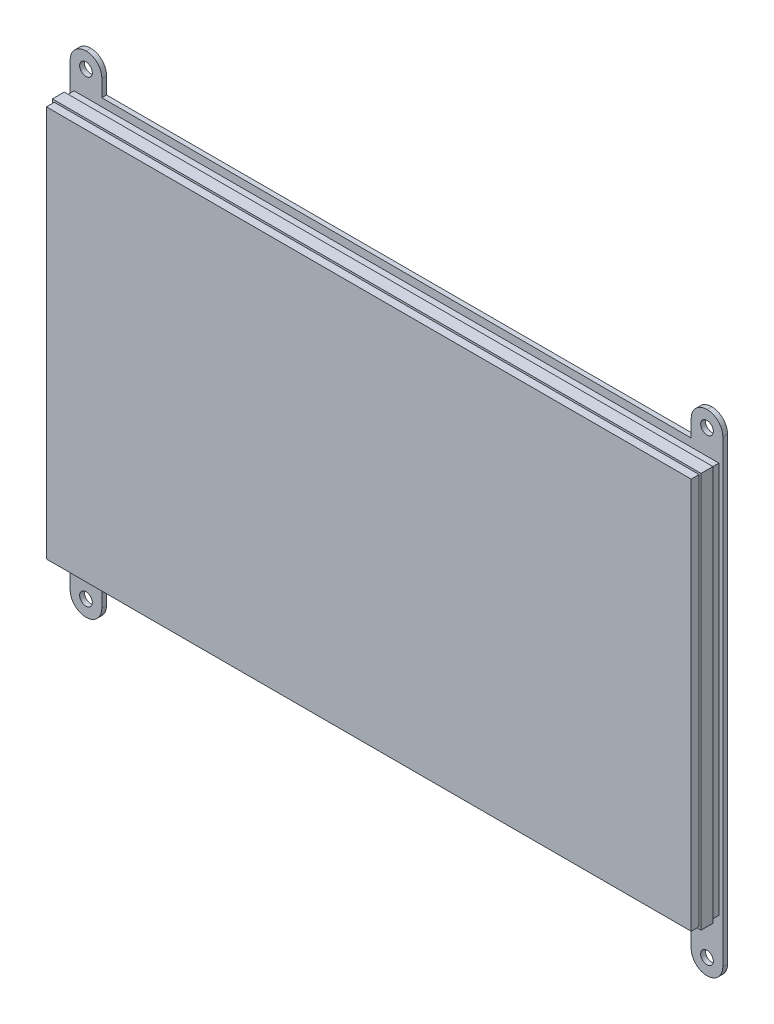
SolidWorks part; units mm, degrees
material "Alliage 2018"
ref_plane "Plan de face" through (0, 0, 0) normal (0, 0, 1) x (1, 0, 0)
ref_plane "Plan de dessus" through (0, 0, 0) normal (0, 1, 0) x (1, 0, 0)
ref_plane "Plan de droite" through (0, 0, 0) normal (1, 0, 0) x (0, 0, -1)
sketch "Esquisse1" plane through (0, 0, 0) normal (0, 0, 1) x (1, 0, 0)
  line L0 (0, 58.5) -> (0, -58.5) construction
  line L1 (-74.5, 53.75) -> (74.5, 53.75)
  line L2 (-82.5, 53.5) -> (-82.5, -53.5)
  line L3 (-74.5, -53.75) -> (74.5, -53.75)
  line L4 (82.5, 53.5) -> (82.5, -53.5)
  line L5 (-82.5, 53.5) -> (82.5, -53.5) construction
  line L6 (-82.5, -53.5) -> (82.5, 53.5) construction
  line L7 (-82, 52.25) -> (82, 52.25)
  line L8 (-82, 52.25) -> (-82, -47.75)
  line L9 (-82, -47.75) -> (82, -47.75)
  line L10 (82, 52.25) -> (82, -47.75)
  line L12 (-82.5, 53.5) -> (-82.5, 58.01)
  line L13 (-78.51, 62) -> (-78.49, 62)
  line L14 (-74.5, 53.75) -> (-74.5, 58.01)
  line L15 (82.5, 0) -> (-82.5, 0) construction
  line L16 (74.5, 53.75) -> (74.5, 58.01)
  line L17 (78.51, 62) -> (78.49, 62)
  line L18 (82.5, 53.5) -> (82.5, 58.01)
  line L19 (-81.5, -47.25) -> (81.5, -47.25)
  line L20 (-81.5, -47.25) -> (-81.5, 51.75)
  line L21 (82.5, -53.5) -> (82.5, -58.01)
  line L22 (78.51, -62) -> (78.49, -62)
  line L23 (74.5, -53.75) -> (74.5, -58.01)
  line L24 (-74.5, -53.75) -> (-74.5, -58.01)
  line L25 (-78.51, -62) -> (-78.49, -62)
  line L26 (-82.5, -53.5) -> (-82.5, -58.01)
  line L27 (-81.5, 51.75) -> (81.5, 51.75)
  line L28 (81.5, -47.25) -> (81.5, 51.75)
  circle A0 centre (-78.5, 58) radius 1.6
  arc A1 (-78.49, 62) -> (-74.5, 58.01) centre (-78.49, 58.01) cw
  arc A2 (-82.5, 58.01) -> (-78.51, 62) centre (-78.51, 58.01) cw
  arc A3 (82.5, 58.01) -> (78.51, 62) centre (78.51, 58.01) ccw
  arc A4 (78.49, 62) -> (74.5, 58.01) centre (78.49, 58.01) ccw
  circle A5 centre (78.5, 58) radius 1.6
  circle A6 centre (78.5, -58) radius 1.6
  arc A7 (78.49, -62) -> (74.5, -58.01) centre (78.49, -58.01) cw
  arc A8 (82.5, -58.01) -> (78.51, -62) centre (78.51, -58.01) cw
  arc A9 (-82.5, -58.01) -> (-78.51, -62) centre (-78.51, -58.01) ccw
  arc A10 (-78.49, -62) -> (-74.5, -58.01) centre (-78.49, -58.01) ccw
  circle A11 centre (-78.5, -58) radius 1.6
  point P0 (0, 0)
  point P21 (-74.5, 62)
  point P24 (-82.5, 62)
  point P34 (82.5, 62)
  point P35 (74.5, 62)
  point P45 (74.5, -62)
  point P46 (82.5, -62)
  point P56 (-82.5, -62)
  point P57 (-74.5, -62)
  dimension "D5" = 4.25
  dimension "D6" = 3.99
  dimension "D1" = 107
  dimension "D2" = 165
  dimension "D3" = 8
  dimension "D4" = 8.5
  dimension "D7" = 1.5
  dimension "D8" = 6
  dimension "D9" = 0.5
  dimension "D10" = 0.5
  dimension "D11" = 0.5
  dimension "D12" = 0.5
  dimension "D13" = 0.5
  dimension "D14" = 0.5
  dimension "D15" = 100
  dimension "D16" = 107.5
extrude "Boss.-Extru.1" add sketch "Esquisse1" against normal blind 1.2 contours A0 | L14 A1 L13 A2 L12 L2 L26 A9 L25 A10 L24 L3 L23 A7 L22 A8 L21 L4 L18 A3 L17 A4 L16 L1 | A5 | A6 | A11 region at (-78.5, 58, 0)
extrude "Boss.-Extru.2" add sketch "Esquisse1<3>" along normal blind 2 contours L27 L28 L19 L20
sketch "Esquisse1<3>" plane through (0, 0, 0) normal (0, 0, 1) x (1, 0, 0) same geometry as "Esquisse1"
sketch "Esquisse3" plane through (0, 0, 2) normal (0, 0, 1) x (1, 0, 0)
  line L0 (-82, 52.25) -> (82, 52.25) construction
  line L1 (-82, 52.25) -> (82, 52.25)
  line L2 (-82, 52.25) -> (-82, -47.75)
  line L3 (-82, -47.75) -> (82, -47.75)
  line L4 (82, 52.25) -> (82, -47.75)
  line L5 (82, 52.25) -> (82, -47.75) construction
  line L7 (-82, 52.25) -> (-82, -47.75) construction
  dimension "D1" = 0
  dimension "D2" = 0
  dimension "D3" = 0
  dimension "D4" = 100
extrude "Boss.-Extru.4" add sketch "Esquisse3" along normal blind 3
sketch "Esquisse4" plane through (0, 0, 5) normal (0, 0, 1) x (1, 0, 0)
  line L1 (-81.5, 51.75) -> (81.5, 51.75)
  line L2 (-81.5, 51.75) -> (-81.5, -47.25)
  line L3 (-81.5, -47.25) -> (81.5, -47.25)
  line L4 (81.5, 51.75) -> (81.5, -47.25)
extrude "Boss.-Extru.5" add sketch "Esquisse4" along normal blind 2
sketch "Esquisse5" plane through (0, 0, -1.2) normal (0, 0, -1) x (-1, 0, 0)
  line L0 (0, 58.5) -> (0, -58.5) construction
  line L1 (-18.75, -29.25) -> (18.75, -29.25)
  line L2 (-18.75, -29.25) -> (-18.75, -34.25)
  line L3 (-18.75, -34.25) -> (18.75, -34.25)
  line L4 (18.75, -29.25) -> (18.75, -34.25)
  line L5 (-18.75, -29.25) -> (18.75, -34.25) construction
  line L6 (-18.75, -34.25) -> (18.75, -29.25) construction
  line L7 (74.5, -53.75) -> (-74.5, -53.75) construction
  line L8 (-82.5, 53.5) -> (-82.5, -53.5) construction
  line L9 (-60, 11.75) -> (-55, 11.75)
  line L10 (-60, 11.75) -> (-60, 9.75)
  line L11 (-60, 9.75) -> (-55, 9.75)
  line L12 (-55, 11.75) -> (-55, 9.75)
  point P0 (0, -31.75)
  dimension "D1" = 37.5
  dimension "D2" = 5
  dimension "D3" = 19.5
  dimension "D4" = 63.5
  dimension "D5" = 2
  dimension "D6" = 22.5
  dimension "D7" = 5
extrude "Enlèv. mat.-Extru.1" cut sketch "Esquisse5" against normal blind 1.2
sketch "Esquisse6" plane through (0, 0, -1.2) normal (0, 0, -1) x (-1, 0, 0)
  line L0 (18.75, -34.25) -> (82.5, -34.25) construction
  line L1 (82.5, 58.01) -> (82.5, -58.01) construction
  text T0 "7inch HDMI Display-C" font "Century Gothic" height in points 14
extrude "Enlèv. mat.-Extru.2" cut sketch "Esquisse6" against normal blind 0.1
sketch "Esquisse7" plane through (0, 0, -1.2) normal (0, 0, -1) x (-1, 0, 0)
  line L0 (76.75, -39.25) -> (18.75, -39.25) construction
  line L2 (-18.75, -34.25) -> (18.75, -34.25) construction
  text T0 "1024 x 600 pixel" font "Century Gothic" height in points 10
  dimension "D1" = 5
  dimension "D2" = 58
extrude "Enlèv. mat.-Extru.3" cut sketch "Esquisse7" against normal blind 0.1
